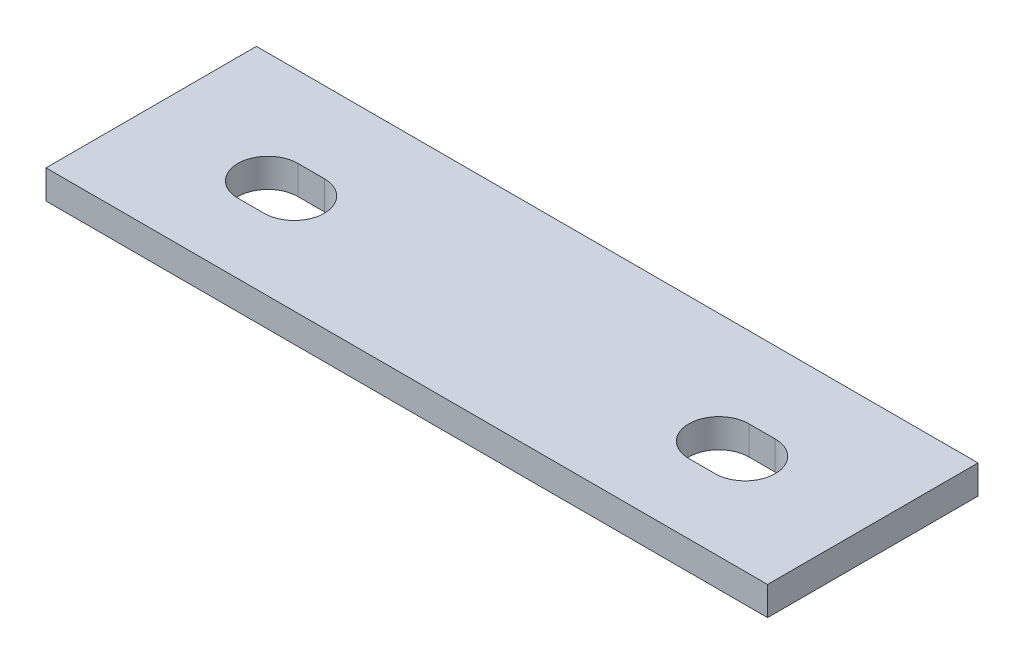
SolidWorks part; units mm, degrees
material "Plain Carbon Steel"
ref_plane "Front Plane" through (0, 0, 0) normal (0, 0, 1) x (1, 0, 0)
ref_plane "Top Plane" through (0, 0, 0) normal (0, 1, 0) x (1, 0, 0)
ref_plane "Right Plane" through (0, 0, 0) normal (1, 0, 0) x (0, 0, -1)
sketch "Sketch2" plane through (0, 0, 0) normal (0, 1, 0) x (1, 0, 0)
  line L1 (0, 0) -> (152.4, 0)
  line L2 (0, 0) -> (0, 44.45)
  line L3 (0, 44.45) -> (152.4, 44.45)
  line L4 (152.4, 0) -> (152.4, 44.45)
  dimension "D1" = 152.4
  dimension "D2" = 44.45
base flange "Base-Flange1" sketch "Sketch2" thickness 6.0731 reverse thickness direction no parameters "D1"=6.35
sketch "Sketch7" plane through (0, -6.0731, 0) normal (0, -1, 0) x (1, 0, 0)
  line L0 (126.6031, -14.7218) -> (121.0469, -14.7218) construction
  line L1 (126.6031, -14.7218) -> (121.0469, -14.7218)
  line L2 (31.3531, -14.7218) -> (25.7969, -14.7218) construction
  line L3 (25.7969, -27.4218) -> (31.3531, -27.4218) construction
  line L4 (121.0469, -27.4218) -> (126.6031, -27.4218) construction
  line L5 (31.3531, -14.7218) -> (25.7969, -14.7218)
  line L6 (25.7969, -27.4218) -> (31.3531, -27.4218)
  line L7 (121.0469, -27.4218) -> (126.6031, -27.4218)
  arc A0 (31.3531, -27.4218) -> (31.3531, -14.7218) centre (31.3531, -21.0718) ccw construction
  arc A1 (121.0469, -14.7218) -> (121.0469, -27.4218) centre (121.0469, -21.0718) ccw construction
  arc A2 (31.3531, -27.4218) -> (31.3531, -14.7218) centre (31.3531, -21.0718) ccw
  arc A3 (121.0469, -14.7218) -> (121.0469, -27.4218) centre (121.0469, -21.0718) ccw
  arc A4 (126.6031, -27.4218) -> (126.6031, -14.7218) centre (126.6031, -21.0718) ccw construction
  arc A5 (31.3531, -27.4218) -> (31.3531, -14.7218) centre (31.3531, -21.0718) ccw
  arc A6 (126.6031, -27.4218) -> (126.6031, -14.7218) centre (126.6031, -21.0718) ccw
  arc A7 (25.7969, -14.7218) -> (25.7969, -27.4218) centre (25.7969, -21.0718) ccw construction
  arc A8 (25.7969, -14.7218) -> (25.7969, -27.4218) centre (25.7969, -21.0718) ccw
extrude "Cut-Extrude1" cut sketch "Sketch7" against normal through all both and the other way through all contours L7 A6 L1 A3 | L5 A8 L6 A2 normal cut yes
sketch "Bend-Lines1" [suppressed] plane through (0, 0, 0) normal (0, 1, 0) x (1, 0, 0)
sketch "Bounding-Box1" [suppressed] plane through (0, 0, 0) normal (0, 1, 0) x (1, 0, 0)
sheet metal parameters "Sheet-Metal1" thickness 6.0731 parameters "D1"=6.35
flat pattern "Flat-Pattern1" [suppressed]
sketch "Bend-Lines2" plane through (0, 0, 0) normal (0, 1, 0) x (1, 0, 0)
sketch3d "Bounding-Box2" [suppressed]
  line L0 (-152.4, 44.45, 0) -> (0, 44.45, 0) construction
  line L1 (-152.4, 0, 0) -> (0, 0, 0) construction
  line L2 (-152.4, 44.45, 0) -> (-152.4, 0, 0) construction
  line L3 (0, 44.45, 0) -> (0, 0, 0) construction
sheet metal parameters "Sheet-Metal2" thickness 6.0731 parameters "D1"=6.35
flat pattern "Flat-Pattern1"
sketch "Bend-Lines2" plane through (0, 0, 0) normal (0, 1, 0) x (1, 0, 0)
sketch3d "Bounding-Box2" [suppressed]
  line L0 (152.4, 44.45, 0) -> (0, 44.45, 0) construction
  line L1 (152.4, 0, 0) -> (0, 0, 0) construction
  line L2 (152.4, 44.45, 0) -> (152.4, 0, 0) construction
  line L3 (0, 44.45, 0) -> (0, 0, 0) construction
